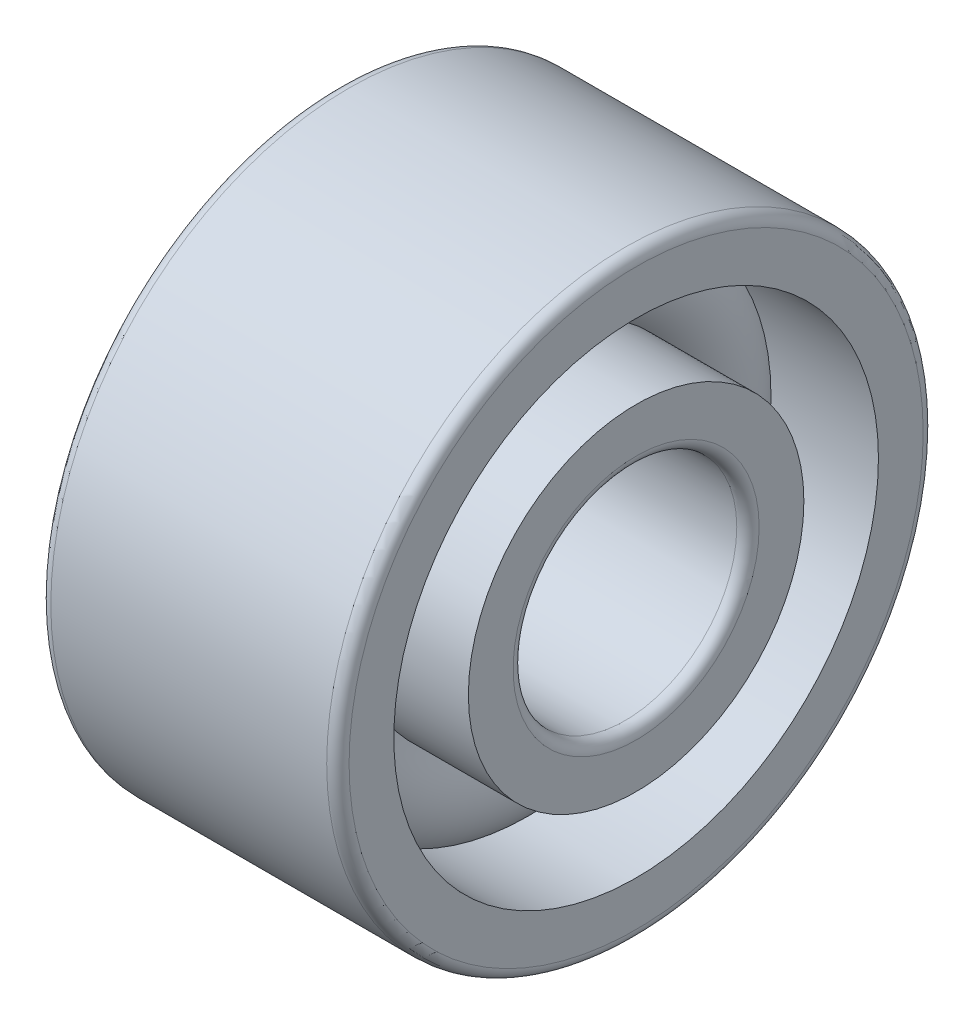
SolidWorks part; units mm, degrees
ref_plane "Plane1" through (0, 0, 0) normal (0, 0, 1) x (1, 0, 0)
ref_plane "Plane2" through (0, 0, 0) normal (0, 1, 0) x (1, 0, 0)
ref_plane "Plane3" through (0, 0, 0) normal (1, 0, 0) x (0, 0, -1)
other "Configuration Table"
sketch "Clipboard" plane through (0, 0, 0) normal (0, 0, 1) x (1, 0, 0)
  line L0 (-10, 0) -> (10, 0) construction
  line L1 (0, 0) -> (22.3471, -0.7804)
  line L2 (0, 0) -> (2.7483, 0.096)
  line L3 (0, 0) -> (22.3471, -0.7804)
  line L4 (0, 0) -> (-22.3573, -0.3902)
sketch "CagSpiSke" plane through (0, 0, 0) normal (0, 0, 1) x (1, 0, 0)
  line L0 (0.075, 2.625) -> (0.075, 2.875)
  line L1 (0.075, 2.875) -> (-0.075, 2.875)
  line L2 (-0.075, 2.875) -> (-0.075, 2.625)
  line L3 (-0.075, 2.625) -> (0.075, 2.625)
  line L4 (-20.6375, 0) -> (20.6375, 0) construction
  line L5 (0, 0) -> (0, 23.7692) construction
revolve "CageSpine" add sketch "CagSpiSke" angle 0.001 about L4 reverse direction yes
ref_axis "Axis1" through (-50, 0, 0) along (1, 0, 0)
sketch "CagBalSke" plane through (0, 0, 0) normal (0, 0, 1) x (1, 0, 0)
  line L0 (-0.825, 2.75) -> (0.825, 2.75)
  line L1 (-1.905, 2.75) -> (1.905, 2.75) construction
  line L2 (-10, 0) -> (10, 0) construction
  line L3 (0, 0) -> (0, 24) construction
  arc A0 (0.825, 2.75) -> (-0.825, 2.75) centre (0, 2.75) cw
revolve "CageBall" [suppressed] add sketch "CagBalSke" angle 360 about L1 reverse direction yes
pattern_circular "CageBalls" [suppressed] count 2 every 180 about axis through (-50, 0, 0) along (1, 0, 0)
sketch "CagTrmODSke" plane through (0, 0, 0) normal (0, 0, 1) x (1, 0, 0)
  line L0 (0.826, 2.875) -> (0.826, 3.576)
  line L1 (0.826, 3.576) -> (-0.826, 3.576)
  line L2 (-0.826, 3.576) -> (-0.826, 2.875)
  line L3 (-0.826, 2.875) -> (0.826, 2.875)
  line L4 (-20.6375, 0) -> (20.6375, 0) construction
  line L5 (0, 0) -> (0, 25) construction
revolve "CageTrimOD" [suppressed] cut sketch "CagTrmODSke" angle 360 about L4 reverse direction yes
sketch "CagTrmIDSke" plane through (0, 0, 0) normal (0, 0, 1) x (1, 0, 0)
  line L0 (0.826, 1.926) -> (0.826, 2.625)
  line L1 (0.826, 2.625) -> (-0.826, 2.625)
  line L2 (-0.826, 2.625) -> (-0.826, 1.926)
  line L3 (-0.826, 1.926) -> (0.826, 1.926)
  line L4 (-20.6375, 0) -> (20.6375, 0) construction
  line L5 (0, 0) -> (0, 25) construction
revolve "CageTrimID" [suppressed] cut sketch "CagTrmIDSke" angle 360 about L4 reverse direction yes
sketch "BalSimSke" plane through (0, 0, 0) normal (0, 0, 1) x (1, 0, 0)
  line L0 (-10, 0) -> (10, 0) construction
  line L1 (-10, 2.75) -> (10, 2.75) construction
  line L2 (0, 0) -> (0, 23) construction
  circle A0 centre (0, 2.75) radius 0.75
revolve "BallsSimplified" add sketch "BalSimSke" angle 360 about L0
sketch "BalDetSke" plane through (0, 0, 0) normal (0, 0, 1) x (1, 0, 0)
  line L0 (-0.75, 2.75) -> (0.75, 2.75)
  line L1 (-1.905, 2.75) -> (1.905, 2.75) construction
  line L2 (0, 0) -> (0, 25) construction
  arc A0 (0.75, 2.75) -> (-0.75, 2.75) centre (0, 2.75) cw
revolve "BallDetailed" [suppressed] add sketch "BalDetSke" angle 360 about L1 reverse direction yes
sketch "InnRacSke" plane through (0, 0, 0) normal (0, 0, 1) x (1, 0, 0)
  line L0 (-0.525, 2.25) -> (-2, 2.25)
  line L1 (-2, 2.25) -> (-2, 1.65)
  line L2 (-1.85, 1.5) -> (1.85, 1.5)
  line L3 (2, 1.65) -> (2, 2.25)
  line L4 (2, 2.25) -> (0.525, 2.25)
  line L5 (-20.6375, 0) -> (20.6375, 0) construction
  line L6 (0, 0) -> (0, 30) construction
  arc A0 (-2, 1.65) -> (-1.85, 1.5) centre (-1.85, 1.65) ccw
  arc A1 (1.85, 1.5) -> (2, 1.65) centre (1.85, 1.65) ccw
  arc A2 (0.525, 2.25) -> (-0.525, 2.25) centre (0, 2.75) cw
  dimension "Fillet_radius" = 0.15
revolve "InnerRace" add sketch "InnRacSke" angle 360 about L5 reverse direction yes
sketch "OutRacSke" plane through (0, 0, 0) normal (0, 0, 1) x (1, 0, 0)
  line L0 (-0.525, 3.25) -> (-2, 3.25)
  line L1 (-2, 3.25) -> (-2, 3.85)
  line L2 (-1.85, 4) -> (1.85, 4)
  line L3 (2, 3.85) -> (2, 3.25)
  line L4 (2, 3.25) -> (0.525, 3.25)
  line L5 (-20.6375, 0) -> (20.6375, 0) construction
  line L6 (0, 0) -> (0, 30) construction
  arc A0 (-2, 3.85) -> (-1.85, 4) centre (-1.85, 3.85) cw
  arc A1 (1.85, 4) -> (2, 3.85) centre (1.85, 3.85) cw
  arc A2 (0.525, 3.25) -> (-0.525, 3.25) centre (0, 2.75) ccw
  dimension "Fillet_radius" = 0.15
revolve "OuterRace" add sketch "OutRacSke" angle 360 about L5 reverse direction yes
pattern_circular "BallsDetailed" [suppressed] count 2 every 180 about axis through (-50, 0, 0) along (1, 0, 0)
equation "\"BallCLRad@Clipboard\" = ( \"OD@OutRacSke\" + \"ID@InnRacSke\" ) / 4"
equation "\"BallCLRad@BalSimSke\" = \"BallCLRad@Clipboard\""
equation "\"BallCLRad@BalDetSke\" = \"BallCLRad@Clipboard\""
equation "\"BallCLRad@InnRacSke\" = \"BallCLRad@Clipboard\""
equation "\"BallCLRad@OutRacSke\" = \"BallCLRad@Clipboard\""
equation "\"Ball_diameter@InnRacSke\" = \"Ball_diameter@BalDetSke\" - 0.05"
equation "\"Ball_diameter@OutRacSke\" = \"Ball_diameter@BalDetSke\" - 0.05"
equation "\"Ball_diameter@BalSimSke\" = \"Ball_diameter@BalDetSke\""
equation "\"Width@OutRacSke\" = \"Width@InnRacSke\""
equation "\"Fillet_radius@OutRacSke\" = \"Fillet_radius@InnRacSke\""
equation "\"Max_count@Clipboard\" = int( 3.14159265 / atn(( \"Ball_diameter@BalDetSke\" / 2) / sqr( \"BallCLRad@Clipboard\"  *  \"BallCLRad@Clipboard\" - ( \"Ball_diameter@BalDetSke\" / 2) *  ( \"Ball_diameter@BalDetSke\" / 2))))"
equation "\"Max_count@Clipboard\" = ((sgn( \"Max_count@Clipboard\" - \"Count@Clipboard\" )-1)*( \"Max_count@Clipboard\" - \"Count@Clipboard\" ))/-2+ \"Count@Clipboard\""
equation "\"Count@BallsDetailed\" = int( \"Show_count@Clipboard\" ) "
equation "\"Count@BallsDetailed\" = ((sgn( \"Count@BallsDetailed\" - \"Max_count@Clipboard\" )-1)*( \"Count@BallsDetailed\" - \"Max_count@Clipboard\" ))/-2+ \"Max_count@Clipboard\""
equation "\"Count@BallsDetailed\" = ((sgn( \"Count@BallsDetailed\" - \"Min_count@Clipboard\" )+1)*( \"Count@BallsDetailed\" - \"Min_count@Clipboard\"))/2 +\"Min_count@Clipboard\""
equation "\"Angle@BallsDetailed\" = 360.0 / \"Max_count@Clipboard\""
equation "\"BallCLRad@CagBalSke\" = \"BallCLRad@Clipboard\""
equation "\"Count@CageBalls\" = \"Count@BallsDetailed\""
equation "\"Angle@CageBalls\" = \"Angle@BallsDetailed\""
equation "\"Angle@CageSpine\" =  \"Angle@CageBalls\" * ( \"Count@CageBalls\" -1 + int( \"Count@CageBalls\" / \"Max_count@Clipboard\" ) )  + 0.001 -  int( \"Count@CageBalls\" / \"Max_count@Clipboard\" ) * 0.001"
equation "\"Angle@CageSpine\" =  \"Angle@CageSpine\" * int( \"Min_count@Clipboard\" / 2) + int(1 / \"Min_count@Clipboard\")  * 0.001"
equation "\"CageWallOD@CagBalSke\" =  \"Ball_diameter@BalDetSke\" * 1.1"
equation "\"Thickness@CagSpiSke\" =  \"Ball_diameter@BalDetSke\" * 0.1"
equation "\"OD@CagTrmODSke\" = \"BallCLRad@Clipboard\" * 2 + \"CageWallOD@CagBalSke\" + 0.002"
equation "\"ID@CagTrmODSke\" = \"BallCLRad@Clipboard\" * 2 + \"Ball_diameter@BalDetSke\" / 6"
equation "\"OD@CagTrmIDSke\" = \"BallCLRad@Clipboard\" * 2 - \"Ball_diameter@BalDetSke\" / 6"
equation "\"ID@CagTrmIDSke\" = \"BallCLRad@Clipboard\" * 2 - \"CageWallOD@CagBalSke\" + 0.002"
equation "\"OD@CagSpiSke\" = \"ID@CagTrmODSke\""
equation "\"ID@CagSpiSke\" = \"OD@CagTrmIDSke\""
equation "\"Width@CagTrmODSke\" = \"CageWallOD@CagBalSke\" + 0.002"
equation "\"Width@CagTrmIDSke\" = \"CageWallOD@CagBalSke\" + 0.002"
